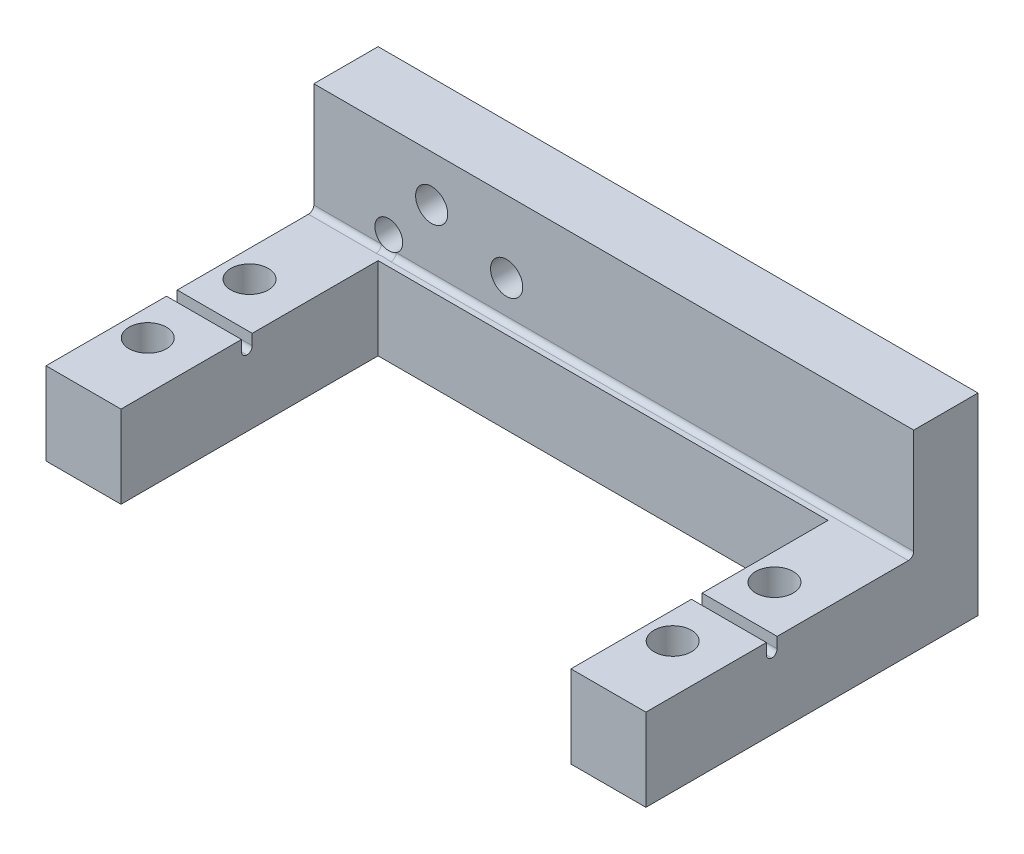
SolidWorks part; units mm, degrees
ref_plane "前视基准面" through (0, 0, 0) normal (0, 0, 1) x (1, 0, 0)
ref_plane "上视基准面" through (0, 0, 0) normal (0, 1, 0) x (1, 0, 0)
ref_plane "右视基准面" through (0, 0, 0) normal (1, 0, 0) x (0, 0, -1)
sketch "草图1" plane through (0, 0, 0) normal (0, 0, 1) x (1, 0, 0)
  line L1 (-29, 6.5) -> (29, 6.5)
  line L2 (-29, 6.5) -> (-29, -6.5)
  line L3 (-29, -6.5) -> (29, -6.5)
  line L4 (29, 6.5) -> (29, -6.5)
  line L5 (-29, 6.5) -> (29, -6.5) construction
  line L6 (-29, -6.5) -> (29, 6.5) construction
  point P0 (0, 0)
  dimension "D1" = 13
  dimension "D2" = 58
extrude "凸台-拉伸1" add sketch "草图1" along normal blind 6
sketch "草图3" plane through (0, 0, 0) normal (0, 0, -1) x (-1, 0, 0)
  line L2 (29, -6.5) -> (-29, -6.5) construction
  line L3 (29, 6.5) -> (29, -6.5) construction
  circle A1 centre (20, -2.2) radius 1.3
  circle A2 centre (9, -0.2) radius 1.5
  dimension "D5" = 2
  dimension "D6" = 2.6
  dimension "D2" = 3
  dimension "D1" = 4.3
  dimension "D3" = 11
  dimension "D4" = 9
sketch "草图9" plane through (0, 0, 6) normal (0, 0, 1) x (1, 0, 0)
  line L0 (29, -6.5) -> (29, 6.5) construction
  line L1 (-29, -6.5) -> (29, -6.5)
  line L2 (-29, -6.5) -> (-29, -3.8)
  line L3 (-29, -3.8) -> (29, -3.8)
  line L4 (29, -6.5) -> (29, -3.8)
  dimension "D1" = 2.7
extrude "凸台-拉伸5" add sketch "草图9" along normal blind 22
sketch "草图10" plane through (0, -3.8, 0) normal (0, 1, 0) x (1, 0, 0)
  line L0 (0, 5.4108) -> (0, -35.4113) construction
  line L1 (-34.803, -19.25) -> (28.3993, -19.25) construction
  line L2 (29, -6) -> (-29, -6) construction
  line L7 (0, -27) -> (0, -7) construction
  line L8 (-24.5, -19.25) -> (24.5, -19.25) construction
  circle A0 centre (-24.5, -24) radius 1.75
  circle A1 centre (-24.5, -14.5) radius 1.75
  circle A2 centre (24.5, -24) radius 1.75
  circle A3 centre (24.5, -14.5) radius 1.75
  point P5 (0, -19.25)
  dimension "D5" = 3.5
  dimension "D1" = 8.5
  dimension "D4" = 4.75
extrude "切除-拉伸6" cut sketch "草图10" against normal through all
sketch "草图11" plane through (0, -3.8, 0) normal (0, 1, 0) x (1, 0, 0)
  line L0 (0, 5.0357) -> (0, -32.1605) construction
  line L1 (-35.0786, -17) -> (29.4366, -17) construction
  line L2 (29, -6) -> (-29, -6) construction
  line L3 (-20, -7) -> (20, -7)
  line L4 (-20, -7) -> (-20, -27)
  line L5 (-20, -27) -> (20, -27)
  line L6 (20, -7) -> (20, -27)
  line L7 (0, -27) -> (0, -7) construction
  line L8 (-20, -17) -> (20, -17) construction
  point P5 (0, -17)
  dimension "D1" = 40
  dimension "D2" = 20
  dimension "D3" = 1
extrude "切除-拉伸7" cut sketch "草图11" against normal through all
sketch "草图13" plane through (0, 0, 28) normal (0, 0, 1) x (1, 0, 0)
  line L0 (-29, -6.5) -> (29, -6.5) construction
  line L1 (-29, 6.5) -> (-27, 6.5)
  line L2 (-29, 6.5) -> (-29, -6.5)
  line L3 (-29, -6.5) -> (-27, -6.5)
  line L4 (-27, 6.5) -> (-27, -6.5)
  dimension "D1" = 2
extrude "切除-拉伸8" cut sketch "草图13" against normal through all
extrude "切除-拉伸9" cut sketch "草图3" against normal blind 10
sketch "草图14" plane through (0, -6.5, 0) normal (0, -1, 0) x (1, 0, 0)
  line L0 (-27, 0) -> (29, 0) construction
  line L1 (-27, 28) -> (-20, 28)
  line L2 (-27, 28) -> (-27, 0)
  line L4 (-20, 27) -> (-20, 7)
  line L5 (-27, 0) -> (-27, 28) construction
  line L6 (-27, 0) -> (-20, 0)
  line L8 (-20, 7) -> (20, 7)
  line L9 (20, 7) -> (20, 27)
  line L10 (-27, 28) -> (29, 28) construction
  line L11 (20, 28) -> (29, 28)
  line L12 (29, 28) -> (29, 0)
  line L13 (29, 0) -> (-20, 0)
  line L14 (-20, 28) -> (20, 28)
  line L15 (-20, 27) -> (20, 27)
extrude "凸台-拉伸6" add sketch "草图14" along normal blind 5
sketch "草图15" plane through (0, -3.8, 0) normal (0, 1, 0) x (1, 0, 0)
  circle A0 centre (-24.5, -14.5) radius 1.75
  circle A1 centre (-24.5, -24) radius 1.75
  circle A2 centre (24.5, -14.5) radius 1.75
  circle A3 centre (24.5, -24) radius 1.75
  dimension "D1" = 3.5
  dimension "D2" = 3.5
  dimension "D3" = 3.5
  dimension "D4" = 3.5
extrude "切除-拉伸10" cut sketch "草图15" against normal through all
sketch "草图16" plane through (0, -3.8, 0) normal (0, 1, 0) x (1, 0, 0)
  line L0 (29, -28) -> (-27, -28) construction
  line L1 (-20, -27) -> (20, -27)
  line L2 (-20, -27) -> (-20, -28)
  line L3 (-20, -28) -> (20, -28)
  line L4 (20, -27) -> (20, -28)
extrude "切除-拉伸11" cut sketch "草图16" against normal blind 10
sketch "草图17" plane through (0, -3.8, 0) normal (0, 1, 0) x (1, 0, 0)
  line L0 (-27, -17) -> (32.4664, -17) construction
  line L1 (-27, -6) -> (-27, -28) construction
  line L2 (0, 7.5093) -> (0, -32.839) construction
  line L13 (20, -28) -> (22, -28)
  line L14 (20, -28) -> (20, -7)
  line L15 (20, -7) -> (22, -7)
  line L16 (22, -28) -> (22, -7)
  dimension "D3" = 2
extrude "切除-拉伸13" cut sketch "草图17" against normal blind 10
sketch "草图18" plane through (0, -3.8, 0) normal (0, 1, 0) x (1, 0, 0)
  line L0 (-24.5, -14.5) -> (-24.5, -24) construction
  line L1 (1, 5.4459) -> (1, -33.7117) construction
  line L8 (-28.1146, -19.25) -> (35.4526, -19.25) construction
  line L9 (-27, -6) -> (-27, -28) construction
  line L10 (-27, -18.75) -> (-20, -18.75)
  line L11 (-27, -18.75) -> (-27, -19.75)
  line L12 (-27, -19.75) -> (-20, -19.75)
  line L13 (-20, -18.75) -> (-20, -19.75)
  line L14 (-20, -7) -> (-20, -28) construction
  line L15 (-27, 0) -> (-27, -6) construction
  line L16 (29, -19.75) -> (22, -19.75)
  line L17 (22, -18.75) -> (22, -19.75)
  line L18 (29, -18.75) -> (22, -18.75)
  line L19 (29, -18.75) -> (29, -19.75)
  dimension "D1" = 0.5
  dimension "D2" = 1
  dimension "D3" = 28
extrude "切除-拉伸14" cut sketch "草图18" against normal blind 1.5
fillet "圆角1" radius 0.5 1 edges at (1, -3.8, 6)
sketch "草图21" plane through (0, 0, 6) normal (0, 0, 1) x (1, 0, 0)
  line L0 (22, -3.8) -> (-20, -3.8) construction
  line L1 (-27, -3.3) -> (-27, 6.5) construction
  circle A0 centre (-16, 2.2) radius 1.5
  dimension "D1" = 3
  dimension "D2" = 6
  dimension "D3" = 11
extrude "切除-拉伸16" cut sketch "草图21" against normal blind 10
fillet "圆角4" radius 0.5 4 edges at (25.5, -5.3, 19.75) (25.5, -5.3, 18.75) (-23.5, -5.3, 19.75) (-23.5, -5.3, 18.75)
sketch "草图23" plane through (0, 0, 28) normal (0, 0, 1) x (1, 0, 0)
  line L1 (-27, -3.8) -> (-20, -3.8)
  line L2 (-27, -3.8) -> (-27, -11.5)
  line L3 (-27, -11.5) -> (-20, -11.5)
  line L4 (-20, -3.8) -> (-20, -11.5)
  line L5 (22, -3.8) -> (29, -3.8)
  line L6 (22, -3.8) -> (22, -11.5)
  line L7 (22, -11.5) -> (29, -11.5)
  line L8 (29, -3.8) -> (29, -11.5)
extrude "凸台-拉伸7" add sketch "草图23" along normal blind 3
